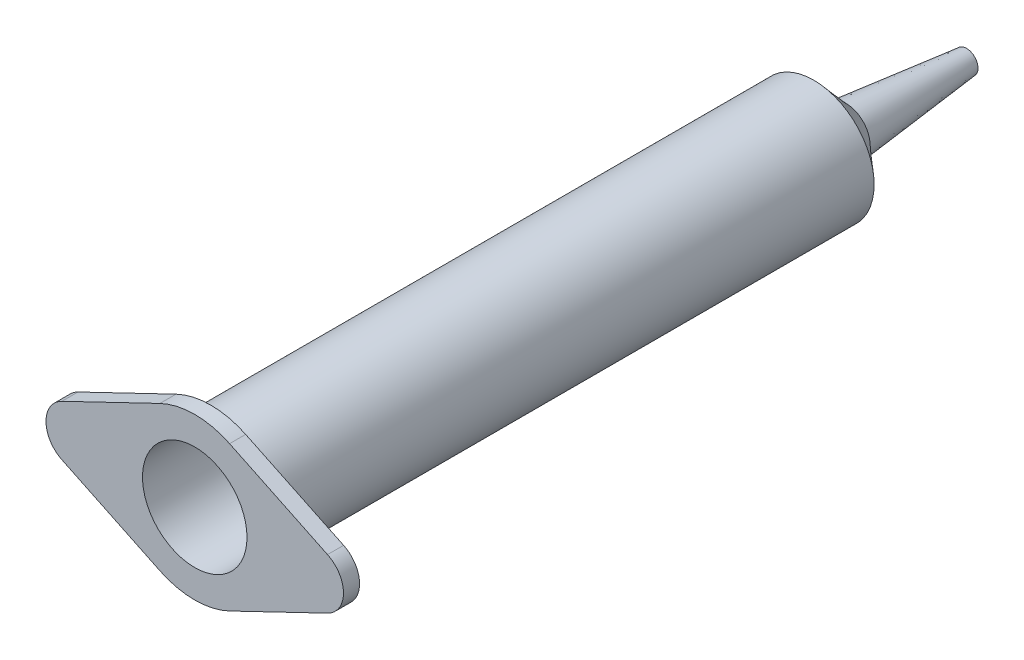
SolidWorks part; units mm, degrees
ref_plane "Front Plane" through (0, 0, 0) normal (0, 0, 1) x (1, 0, 0)
ref_plane "Top Plane" through (0, 0, 0) normal (0, 1, 0) x (1, 0, 0)
ref_plane "Right Plane" through (0, 0, 0) normal (1, 0, 0) x (0, 0, -1)
sketch "Sketch1" plane through (0, 0, 0) normal (0, 1, 0) x (1, 0, 0)
  line L0 (0, 25.6295) -> (0, -26.3849) construction
  line L1 (0, 0) -> (-10, 0)
  line L2 (-10, 0) -> (-10, 2)
  line L3 (-10, 2) -> (-7.5, 2)
  line L4 (-7.5, 2) -> (-7.5, 77)
  line L5 (-7.5, 77) -> (0, 77)
  line L6 (0, 77) -> (0, 0)
  dimension "D1" = 7.5
  dimension "D2" = 10
  dimension "D3" = 2
  dimension "D4" = 75
revolve "Revolve1" add sketch "Sketch1" angle 360 about L0
ref_plane "Plane1" through (0, 0, -81) normal (0, 0, -1) x (-1, 0, 0)
sketch "Sketch2" plane through (0, 0, -81) normal (0, 0, -1) x (-1, 0, 0)
  circle A0 centre (0, 0) radius 3
  dimension "D1" = 6
extrude "Boss-Extrude1" add sketch "Sketch2" along normal blind 15 draft 6 contours A0
sketch "Sketch5" plane through (0, 0, 0) normal (1, 0, 0) x (0, 0, -1)
  line L0 (79.7045, 0) -> (77.3387, 6.5)
  line L1 (0, 0) -> (79.7045, 0)
  line L2 (0, 0) -> (0, 6.5)
  line L3 (0, 6.5) -> (77.3387, 6.5)
  point P1 (79.7045, 0)
  dimension "D1" = 70
  dimension "D2" = 6.5
loft "Loft2" add section edge at (-7.5, 0, -77) section edge at (-3, 0, -81) connector at (-6.7248, 3.3207, -77) connector at (-2.229, 2.0079, -81)
revolve "Cut-Revolve3" cut sketch "Sketch5" angle 360 about L1
sketch "Sketch9" plane through (0, 0, 0) normal (0, 0, 1) x (1, 0, 0)
  circle A0 centre (0, 0) radius 1.1633
sketch "Sketch8" plane through (0, 0, 0) normal (0, 0, 1) x (1, 0, 0)
  line L0 (0, 10.7669) -> (0, 0) construction
  line L1 (0, 0) -> (-15, 0) construction
  line L2 (-4.3333, 9.0123) -> (-16.5167, 3.1543)
  line L3 (-16.5167, -3.1543) -> (-4.3333, -9.0123)
  line L4 (16.5167, -3.1543) -> (4.3333, -9.0123)
  line L5 (4.3333, 9.0123) -> (16.5167, 3.1543)
  arc A0 (-16.5167, 3.1543) -> (-16.5167, -3.1543) centre (-15, 0) ccw
  arc A1 (16.5167, 3.1543) -> (16.5167, -3.1543) centre (15, 0) cw
  circle A2 centre (0, 0) radius 10 construction
  circle A3 centre (0, 0) radius 10
  circle M6 centre (0, 0) radius 10
  dimension "D1" = 7
  dimension "D2" = 15
extrude "Boss-Extrude3" add sketch "Sketch8" against normal up to surface (2 mm away) contours L2 A0 L3 M6 | A1 L5 L4 M6 region at (-12.7135, 0, 0) region at (12.7135, 0, 0) up to face at (-10, 0, -2)
sketch "Sketch10" plane through (0, 0, 0) normal (1, 0, 0) x (0, 0, -1)
  line L0 (99.7828, 0) -> (78.2991, 0)
  line L1 (78.2991, 0) -> (78.2991, 2.9202)
  line L2 (78.2991, 2.9202) -> (99.7828, 0.6622)
  line L3 (99.7828, 0.6622) -> (99.7828, 0)
  dimension "D1" = 6
revolve "Cut-Revolve4" cut sketch "Sketch10" angle 360 about L0
